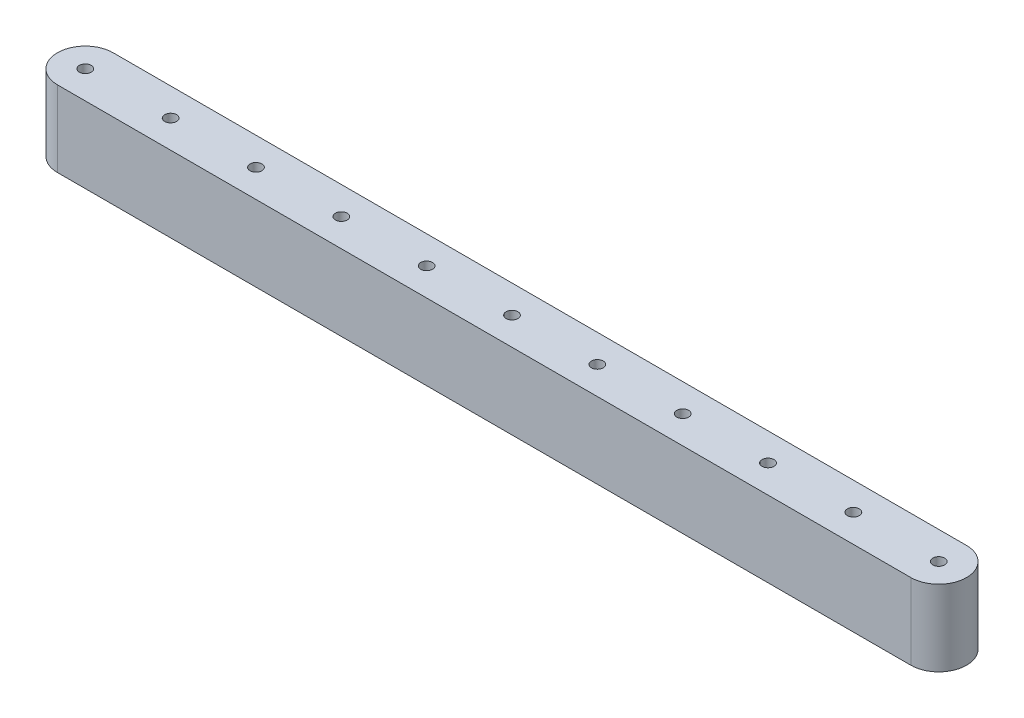
SolidWorks part; units mm, degrees
material "ABS"
ref_plane "Front Plane" through (0, 0, 0) normal (0, 0, 1) x (1, 0, 0)
ref_plane "Top Plane" through (0, 0, 0) normal (0, 1, 0) x (1, 0, 0)
ref_plane "Right Plane" through (0, 0, 0) normal (1, 0, 0) x (0, 0, -1)
sketch "Sketch1" plane through (0, 0, 0) normal (0, 1, 0) x (1, 0, 0)
  line L0 (-73.025, 0) -> (73.025, 0) construction
  line L1 (-73.025, 4.7625) -> (73.025, 4.7625)
  line L2 (-73.025, -4.7625) -> (73.025, -4.7625)
  arc A0 (-73.025, 4.7625) -> (-73.025, -4.7625) centre (-73.025, 0) ccw
  arc A1 (73.025, -4.7625) -> (73.025, 4.7625) centre (73.025, 0) ccw
  point P2 (0, 0)
  dimension "D3" = 9.525
  dimension "D1" = 146.05
extrude "Boss-Extrude1" add sketch "Sketch1" along normal mid plane 13
sketch "Sketch2" plane through (0, 0, 0) normal (0, 1, 0) x (1, 0, 0)
  circle A0 centre (-73.025, 0) radius 1.016
  circle A10 centre (-58.42, 0) radius 1.016
  circle A12 centre (-43.815, 0) radius 1.016
  circle A13 centre (-29.21, 0) radius 1.016
  circle A14 centre (-14.605, 0) radius 1.016
  circle A15 centre (0, 0) radius 1.016
  circle A16 centre (14.605, 0) radius 1.016
  circle A17 centre (29.21, 0) radius 1.016
  circle A18 centre (43.815, 0) radius 1.016
  circle A19 centre (58.42, 0) radius 1.016
  circle A20 centre (73.025, 0) radius 1.016
  point P4 (73.025, 0)
  dimension "D1" = 2.032
extrude "Cut-Extrude1" cut sketch "Sketch2" against normal through all both and the other way through all
equation "\"Num_Holes\"=10"
equation "\"D1@LPattern1\"=\"Num_Holes\""
equation "\"thicknes\"= 13mm"
equation "\"D1@Boss-Extrude1\"=\"thicknes\""
